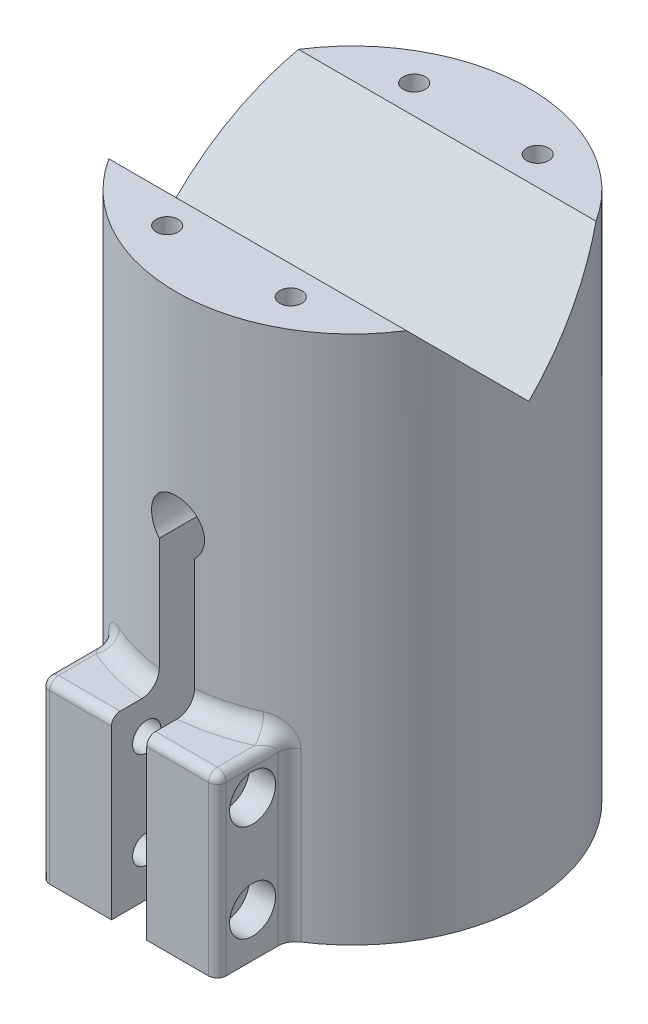
SolidWorks part; units mm, degrees
ref_plane "Front Plane" through (0, 0, 0) normal (0, 0, 1) x (1, 0, 0)
ref_plane "Top Plane" through (0, 0, 0) normal (0, 1, 0) x (1, 0, 0)
ref_plane "Right Plane" through (0, 0, 0) normal (1, 0, 0) x (0, 0, -1)
sketch "Sketch1" plane through (0, 0, 0) normal (0, 1, 0) x (1, 0, 0)
  circle A0 centre (0, 0) radius 20
  dimension "D1" = 40
extrude "Boss-Extrude1" add sketch "Sketch1" along normal blind 60
sketch "Sketch3" plane through (0, 0, 0) normal (0, -1, 0) x (1, 0, 0)
  circle A0 centre (0, 0) radius 12.6
  dimension "D1" = 25.2
extrude "Cut-Extrude1" cut sketch "Sketch3" against normal blind 40
sketch "Sketch5" plane through (0, 0, 0) normal (0, -1, 0) x (-1, 0, 0)
  line L1 (10, -25.3205) -> (-10, -25.3205)
  line L2 (10, -25.3205) -> (10, -17.3205)
  line L4 (-10, -25.3205) -> (-10, -17.3205)
  arc A2 (-10, -17.3205) -> (10, -17.3205) centre (0, 0) ccw
  dimension "D5" = 20
  dimension "D1" = 20
  dimension "D2" = 10
  dimension "D4" = 8
extrude "Boss-Extrude3" add sketch "Sketch5" against normal blind 20
sketch "Sketch6" plane through (0, 0, 0) normal (1, 0, 0) x (0, 0, -1)
  line L0 (0, 49.252) -> (10.748, 60)
  line L1 (0, 49.252) -> (-10.748, 60)
  line L2 (10.748, 60) -> (0, 70.748)
  line L3 (-10.748, 60) -> (0, 70.748)
  line L4 (0, 49.252) -> (0, 70.748) construction
  line L5 (10.748, 60) -> (-10.748, 60) construction
  line L6 (20, 60) -> (-20, 60) construction
  point P1 (0, 60)
  dimension "D1" = 15.2
  dimension "D2" = 15.2
  dimension "D3" = 0
extrude "Cut-Extrude2" cut sketch "Sketch6" against normal blind 20 and the other way blind 20
sketch "Sketch7" plane through (0, 0, 0) normal (0, -1, 0) x (1, 0, 0)
  line L0 (10, 25.3205) -> (-10, 25.3205) construction
  line L1 (2, 10.3205) -> (-2, 10.3205)
  line L2 (2, 10.3205) -> (2, 25.3205)
  line L3 (2, 25.3205) -> (-2, 25.3205)
  line L4 (-2, 10.3205) -> (-2, 25.3205)
  dimension "D1" = 4
  dimension "D2" = 2
  dimension "D3" = 15
extrude "Cut-Extrude3" cut sketch "Sketch7" against normal blind 38
sketch "Sketch8" plane through (0, 0, 0) normal (0, 0, 1) x (1, 0, 0)
  circle A0 centre (0, 37) radius 3
  dimension "D1" = 6
  dimension "D2" = 37
extrude "Cut-Extrude4" cut sketch "Sketch8" along normal blind 20 contours A0
fillet "Fillet1" radius 1 6 edges at (-6, 20, 25.3205) (-10, 20, 21.3205) (10, 20, 21.3205) (6, 20, 25.3205) (-10, 10, 25.3205) (10, 10, 25.3205)
fillet "Fillet2" radius 2 6 edges at (5.5937, 20, 19.2018) (9.6887, 19.725, 17.4965) (-5.5937, 20, 19.2018) (-9.8257, 19.5641, 17.42) (10, 9.5, 17.3205) (-10, 9.5, 17.3205)
sketch "Sketch9" plane through (10, 0, 0) normal (1, 0, 0) x (0, 0, -1)
  line L0 (-25.3205, 0) -> (-25.3205, 19) construction
  line L1 (-18.4391, 0) -> (-24.3205, 0) construction
  line L2 (-24.3205, 20) -> (-20.0749, 20) construction
  circle A0 centre (-21.3205, 5) radius 1.6
  circle A1 centre (-21.3205, 16) radius 1.6
  dimension "D1" = 3.2
  dimension "D4" = 3.2
  dimension "D2" = 4
  dimension "D3" = 5
  dimension "D5" = 4
  dimension "D6" = 4
extrude "Cut-Extrude5" cut sketch "Sketch9" against normal blind 20
sketch "Sketch10" plane through (10, 0, 0) normal (1, 0, 0) x (0, 0, -1)
  circle A0 centre (-21.3205, 5) radius 2.6
  circle A1 centre (-21.3205, 16) radius 2.6
  dimension "D1" = 5.2
  dimension "D2" = 5.2
extrude "Cut-Extrude6" cut sketch "Sketch10" against normal blind 3
sketch "Sketch11" plane through (-10, 0, 0) normal (-1, 0, 0) x (0, 0, 1)
  line L1 (24.3227, 16) -> (22.8216, 18.6)
  line L2 (22.8216, 18.6) -> (19.8194, 18.6)
  line L3 (19.8194, 18.6) -> (18.3183, 16)
  line L4 (18.3183, 16) -> (19.8194, 13.4)
  line L5 (19.8194, 13.4) -> (22.8216, 13.4)
  line L6 (22.8216, 13.4) -> (24.3227, 16)
  line L7 (24.3227, 5) -> (22.8216, 7.6)
  line L8 (22.8216, 7.6) -> (19.8194, 7.6)
  line L9 (19.8194, 7.6) -> (18.3183, 5)
  line L10 (18.3183, 5) -> (19.8194, 2.4)
  line L11 (19.8194, 2.4) -> (22.8216, 2.4)
  line L12 (22.8216, 2.4) -> (24.3227, 5)
  circle A0 centre (21.3205, 16) radius 2.6 construction
  circle A1 centre (21.3205, 5) radius 2.6 construction
  dimension "D1" = 5.2
  dimension "D2" = 5.2
extrude "Cut-Extrude7" cut sketch "Sketch11" against normal blind 3
sketch "Sketch12" plane through (0, 60, 0) normal (0, 1, 0) x (1, 0, 0)
  circle A0 centre (-7, 14) radius 1.25
  circle A1 centre (-7, -14) radius 1.25
  circle A2 centre (7, 14) radius 1.25
  circle A3 centre (7, -14) radius 1.25
  dimension "D3" = 2.5
  dimension "D4" = 2.5
  dimension "D7" = 2.5
  dimension "D8" = 2.5
  dimension "D1" = 14
  dimension "D2" = 14
  dimension "D5" = 7
  dimension "D6" = 7
  dimension "D9" = 7
  dimension "D10" = 7
  dimension "D11" = 14
  dimension "D12" = 14
extrude "Cut-Extrude10" cut sketch "Sketch12" against normal blind 15
